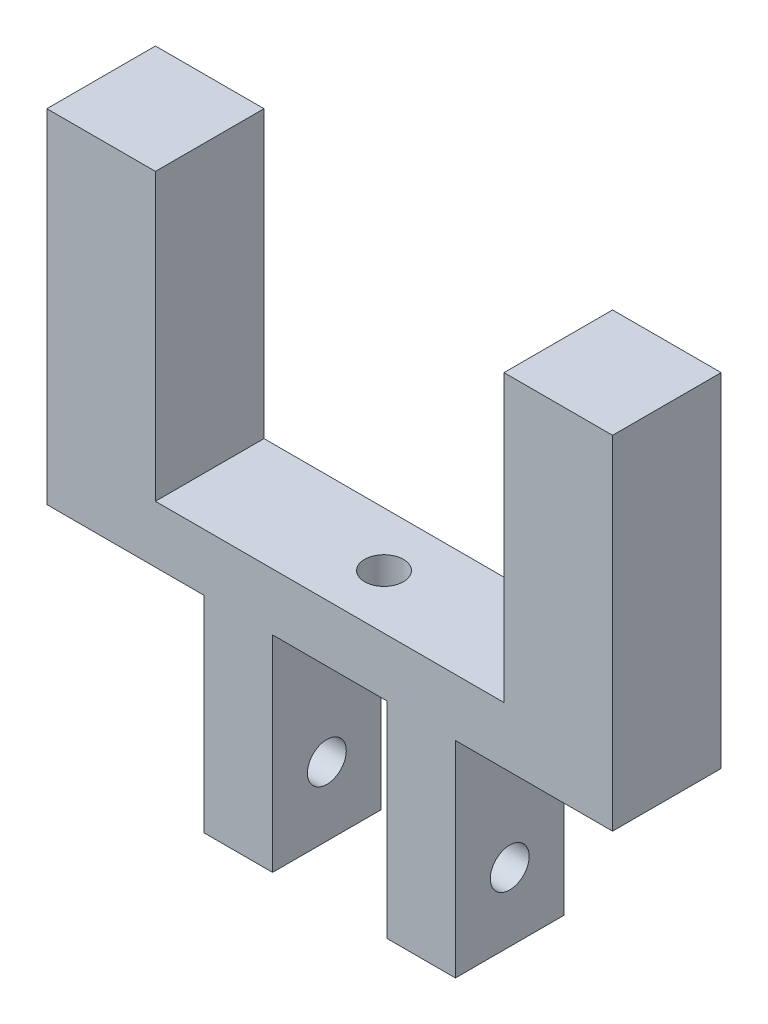
SolidWorks part; units mm, degrees
ref_plane "Plano frontal" through (0, 0, 0) normal (0, 0, 1) x (1, 0, 0)
ref_plane "Plano superior" through (0, 0, 0) normal (0, 1, 0) x (1, 0, 0)
ref_plane "Plano direito" through (0, 0, 0) normal (1, 0, 0) x (0, 0, -1)
sketch "Esboço1" plane through (0, 0, 0) normal (0, 0, 1) x (1, 0, 0)
  line L0 (-24.75, 0) -> (-24.75, -30)
  line L1 (-5, -40) -> (-5, -30)
  line L2 (-11, -48) -> (-5, -48)
  line L3 (-5, -48) -> (-5, -40)
  line L4 (-24.75, -30) -> (-11, -30)
  line L5 (-5, -30) -> (0, -30)
  line L6 (0, -30) -> (0, -25)
  line L7 (0, -25) -> (-15.25, -25)
  line L8 (-15.25, -25) -> (-15.25, 0)
  line L9 (-15.25, 0) -> (-24.75, 0)
  line L10 (0, 0) -> (0, -14.023) construction
  line L11 (-11, -48) -> (-11, -30)
  point P13 (-20, 0)
  point P41 (-5, -44)
  dimension "D1" = 9.5
  dimension "D2" = 40
  dimension "D3" = 25
  dimension "D4" = 5
  dimension "D5" = 0
  dimension "D6" = 6
  dimension "D7" = 10
  dimension "D8" = 14
  dimension "D9" = 8
extrude "Ressalto-extrusão1" add sketch "Esboço1" along normal blind 9.5
mirror "Espelhar1" about plane through (0, -30, 9.5) normal (-1, 0, 0) of "Ressalto-extrusão1"
sketch "Esboço2" plane through (11, 0, 0) normal (1, 0, 0) x (0, 0, -1)
  line L0 (-9.5, -48) -> (0, -48) construction
  circle A0 centre (-4.75, -42) radius 1.7
  point P5 (-4.75, -48)
  dimension "D2" = 3.4
  dimension "D1" = 6
extrude "Corte-extrusão1" cut sketch "Esboço2" against normal through all
sketch "Esboço3" plane through (0, 0, 0) normal (0, 1, 0) x (1, 0, 0)
  line L0 (-15.25, -9.5) -> (-15.25, 0) construction
  circle A0 centre (0, -4.75) radius 1.7
  point P5 (-15.25, -4.75)
  dimension "D1" = 3.4
extrude "Corte-extrusão2" cut sketch "Esboço3" against normal through all
